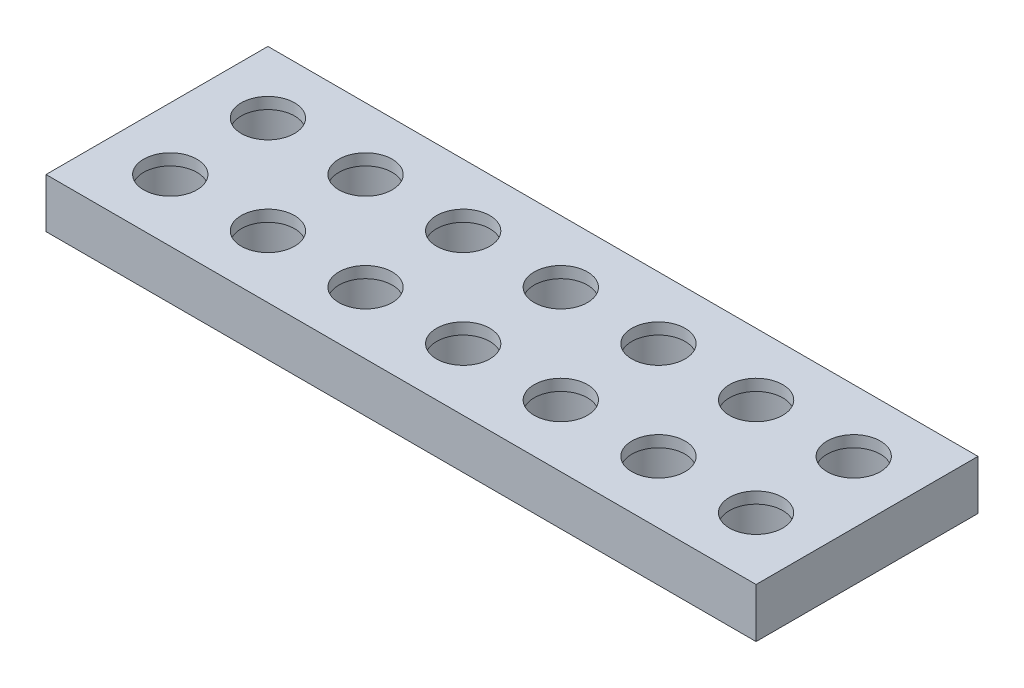
SolidWorks part; units mm, degrees
ref_plane "Front Plane" through (0, 0, 0) normal (0, 0, 1) x (1, 0, 0)
ref_plane "Top Plane" through (0, 0, 0) normal (0, 1, 0) x (1, 0, 0)
ref_plane "Right Plane" through (0, 0, 0) normal (1, 0, 0) x (0, 0, -1)
sketch "Sketch3" plane through (0, 0, 0) normal (0, 1, 0) x (1, 0, 0)
  line L0 (0, 0) -> (25.65, 0) construction
  line L1 (0, 0) -> (0, 25.65) construction
  line L5 (153.9, 25.65) -> (128.25, 25.65) construction
  line L6 (-16.325, 41.975) -> (170.225, 41.975)
  line L7 (-16.325, 41.975) -> (-16.325, -16.325)
  line L8 (-16.325, -16.325) -> (170.225, -16.325)
  line L9 (170.225, 41.975) -> (170.225, -16.325)
  circle A14 centre (0, 0) radius 11.325
  circle A15 centre (25.65, 0) radius 11.325
  circle A16 centre (51.3, 0) radius 11.325
  circle A17 centre (76.95, 0) radius 11.325
  circle A18 centre (102.6, 0) radius 11.325
  circle A19 centre (128.25, 0) radius 11.325
  circle A20 centre (153.9, 0) radius 11.325
  circle A21 centre (25.65, 25.65) radius 11.325
  circle A22 centre (51.3, 25.65) radius 11.325
  circle A23 centre (76.95, 25.65) radius 11.325
  circle A24 centre (102.6, 25.65) radius 11.325
  circle A25 centre (128.25, 25.65) radius 11.325
  circle A26 centre (153.9, 25.65) radius 11.325
  circle A27 centre (0, 25.65) radius 11.325
  circle A42 centre (153.9, 25.65) radius 7
  circle A43 centre (128.25, 25.65) radius 7
  circle A44 centre (102.6, 25.65) radius 7
  circle A45 centre (76.95, 25.65) radius 7
  circle A46 centre (51.3, 25.65) radius 7
  circle A47 centre (25.65, 25.65) radius 7
  circle A48 centre (0, 25.65) radius 7
  circle A49 centre (128.25, 0) radius 7
  circle A50 centre (102.6, 0) radius 7
  circle A51 centre (76.95, 0) radius 7
  circle A52 centre (51.3, 0) radius 7
  circle A53 centre (25.65, 0) radius 7
  circle A54 centre (0, 0) radius 7
  circle A55 centre (153.9, 0) radius 7
  point P17 (128.068, 25.65)
  point P25 (128.9241, 0)
  point P36 (0, 0)
  dimension "D1" = 22.65
  dimension "D10" = 14
  dimension "D4" = 25.65
  dimension "D5" = 25.65
  dimension "D6" = 5
  dimension "D7" = 5
  dimension "D8" = 5
  dimension "D9" = 5
  dimension "D2" = 7
  dimension "D3" = 2
extrude "Boss-Extrude1" add sketch "Sketch3" along normal blind 10 contours L9 L6 L7 L8 A27 A26 A25 A24 A23 A22 A21 A20 A19 A18 A17 A16 A15 A14 region at (76.95, 0, -12.825)
extrude "Boss-Extrude3" add sketch "Sketch3<5>" along normal blind 3 from offset 10 contours A27 A48 | A14 A54 | A21 A47 | A15 A53 | A22 A46 | A16 A52 | A23 A45 | A17 A51 | A24 A44 | A18 A50 | A25 A43 | A19 A49 | A26 A42 | A20 A55 | L9 L6 L7 L8 A27 A26 A25 A24 A23 A22 A21 A20 A19 A18 A17 A16 A15 A14 region at (76.95, 0, -12.825) region at (-11.0047, 0, 0) region at (14.6453, 0, 0) region at (40.2953, 0, 0) region at (65.9453, 0, 0) region at (91.5953, 0, 0) region at (117.2453, 0, 0) region at (142.8953, 0, 0) region at (14.6453, 0, -25.65) region at (40.2953, 0, -25.65) region at (65.9453, 0, -25.65) region at (91.5953, 0, -25.65) region at (117.2453, 0, -25.65) region at (142.8953, 0, -25.65) region at (-11.0047, 0, -25.65)
sketch "Sketch3<5>" plane through (0, 0, 0) normal (0, 1, 0) x (1, 0, 0) same geometry as "Sketch3"
equation "\"diamete\"=22.65"
equation "\"D1@Sketch3\"=\"diamete\""
equation "\"D5@Sketch3\"=\"diamete\"+3"
equation "\"D4@Sketch3\"=\"diamete\"+3"
equation "\"D6@Sketch3\"=5mm"
equation "\"D7@Sketch3\"=5mm"
equation "\"D8@Sketch3\"=5mm"
